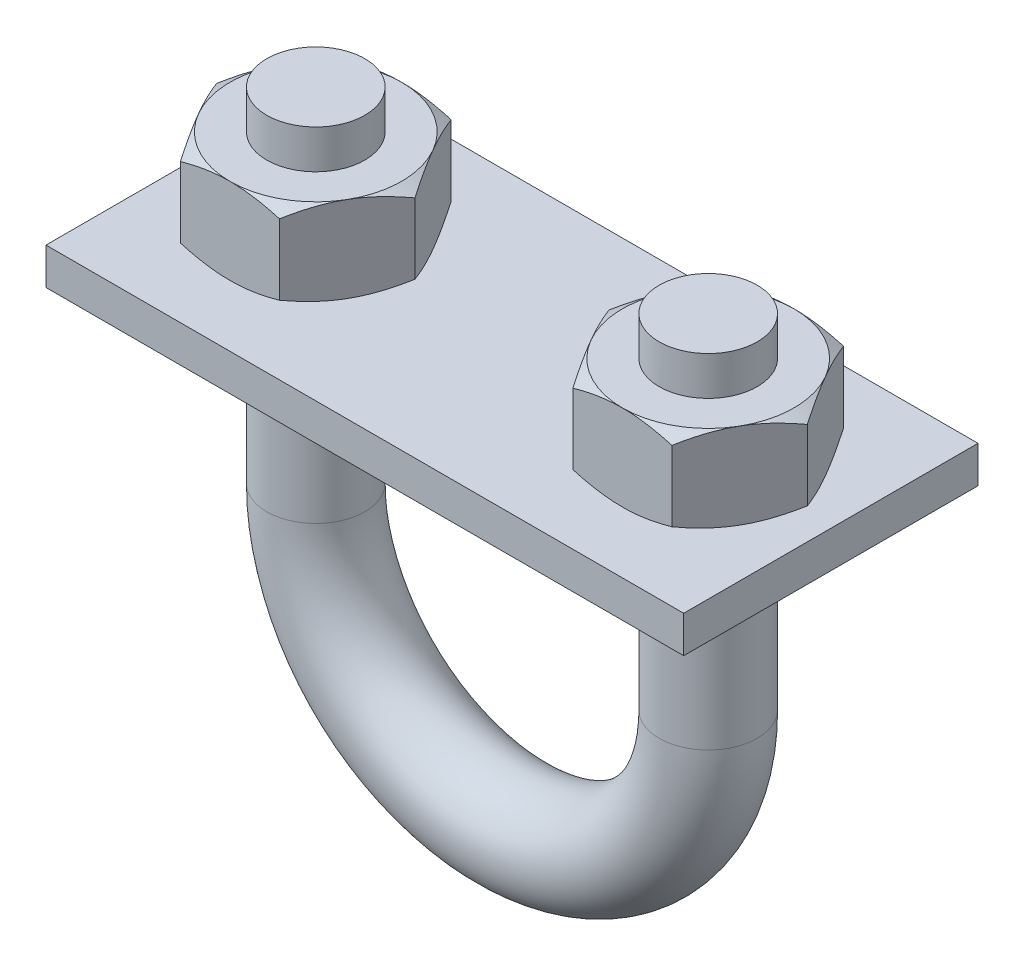
SolidWorks part; units mm, degrees
ref_plane "Front" through (0, 0, 0) normal (0, 0, 1) x (1, 0, 0)
ref_plane "Top" through (0, 0, 0) normal (0, 1, 0) x (1, 0, 0)
ref_plane "Right" through (0, 0, 0) normal (1, 0, 0) x (0, 0, -1)
sketch "Sketch1" plane through (0, 0, 0) normal (0, 0, 1) x (1, 0, 0)
  line L0 (-9.525, 22.225) -> (-15.875, 22.225) construction
  line L1 (-12.7, 22.225) -> (-12.7, 0) construction
  line L3 (12.7, 0) -> (12.7, 22.225) construction
  line L4 (15.875, 22.225) -> (9.525, 22.225) construction
  line L5 (-9.525, 6.35) -> (-15.875, 6.35)
  line L6 (0, -9.525) -> (0, -15.875) construction
  arc A0 (-12.7, 0) -> (12.7, 0) centre (0, 0) ccw construction
  circle A1 centre (0, 0) radius 9.525 construction
  point P5 (0, -12.7)
  point P8 (-12.7, 16.9333)
  point P15 (-12.7, 11.6417)
  dimension "Dia" = 6.35
  dimension "D5" = 5.2917
  dimension "D6" = 5.2917
ref_plane "Plane3" through (0, 22.225, 0) normal (0, 1, 0) x (-1, 0, 0)
sketch "Sketch2" plane through (0, 22.225, 0) normal (0, 1, 0) x (-1, 0, 0)
  circle A0 centre (12.7, 0) radius 3.175
extrude "Boss-Extrude1" add sketch "Sketch2" against normal up to vertex (15.875 mm away) up to point (-9.525, 6.35, 0)
sketch "Sketch6" plane through (0, 22.225, 0) normal (0, 1, 0) x (1, 0, 0)
  circle A1 centre (-12.7, 0) radius 3.175
  circle A2 centre (-12.7, 0) radius 3.175
  dimension "D1" = 0
curve "Helix/Spiral1" pitch 1.27 height 17.145 turns 13.5 parameters "Pitch"=1.27
chamfer "Chamfer2" [suppressed] distance 0.9525 angle 45
sketch "Sketch4" plane through (0, 0, 0) normal (0, 0, 1) x (1, 0, 0)
  line L0 (-9.525, 22.225) -> (-9.525, 23.3362)
  line L1 (-9.525, 23.3362) -> (-10.3499, 22.86)
  line L2 (-10.3499, 22.86) -> (-10.3499, 22.7012)
  line L3 (-10.3499, 22.7012) -> (-9.525, 22.225)
  line L4 (-10.3499, 22.7806) -> (-9.525, 22.7806) construction
  line L5 (-9.9374, 23.0981) -> (-9.9374, 22.4631) construction
  line L7 (-9.525, 22.225) -> (-15.875, 22.225) construction
  dimension "D1" = 60
  dimension "D2" = 0.635
  dimension "D3" = 0.1588
sweep "Threads" [suppressed] cut profiles "Sketch4" path "Helix/Spiral1"
ref_plane "Plane5" through (0, 6.35, 0) normal (0, 1, 0) x (-1, 0, 0)
sketch "Sketch7" plane through (0, 6.35, 0) normal (0, 1, 0) x (-1, 0, 0)
  line L0 (9.525, 0) -> (15.875, 0) construction
  circle A0 centre (12.7, 0) radius 3.175
  circle A1 centre (12.7, 0) radius 3.175 construction
sketch "Sketch8" plane through (0, 0, 0) normal (0, 0, 1) x (1, 0, 0)
  line L0 (-12.7, 22.225) -> (-12.7, 0) construction
  line L1 (12.7, 0) -> (12.7, 22.225) construction
  line L2 (-12.7, 6.35) -> (-12.7, 0)
  line L3 (12.7, 0) -> (12.7, 6.35)
  line L4 (47.1487, 6.35) -> (-47.1487, 6.35) construction
  arc A0 (-12.7, 0) -> (12.7, 0) centre (0, 0) ccw construction
  arc A1 (-12.7, 0) -> (12.7, 0) centre (0, 0) ccw
sweep "Sweep1" add profiles "Sketch7" path "Sketch8"
move or copy body "Body-Move/Copy1" bodies to move or copy 109 copy yes number of copies 1 translate (25.4, 0, 0)
combine bodies "Combine1" operation type add bodies to combine 109 112 111
ref_plane "Plane6" through (0, 16.9333, 0) normal (0, 1, 0) x (-1, 0, 0)
sketch "Sketch9" plane through (0, 16.9333, 0) normal (0, 1, 0) x (-1, 0, 0)
  line L0 (-15.875, 0) -> (-9.525, 0) construction
  line L1 (-15.9079, 5.5562) -> (-19.1158, 0)
  line L2 (-19.1158, 0) -> (-15.9079, -5.5563)
  line L3 (-15.9079, -5.5563) -> (-9.4921, -5.5563)
  line L4 (-9.4921, -5.5563) -> (-6.2842, 0)
  line L5 (-6.2842, 0) -> (-9.4921, 5.5562)
  line L6 (-9.4921, 5.5562) -> (-15.9079, 5.5562)
  circle A0 centre (-12.7, 0) radius 5.5562 construction
  circle A1 centre (-12.7, 0) radius 3.175
  circle A2 centre (12.7, 0) radius 3.175 construction
  dimension "Nut Size" = 11.1125
extrude "Boss-Extrude2" add sketch "Sketch9" along normal mid plane 5.5562 separate body
sketch "Sketch10" plane through (0, 19.7115, 0) normal (0, 1, 0) x (1, 0, 0)
  circle A0 centre (12.7, 0) radius 5.5562 construction
  circle A1 centre (12.7, 0) radius 5.5562
extrude "Cut-Extrude1" cut sketch "Sketch10" against normal through all draft 60 flip side to cut
sketch "Sketch11" plane through (0, 14.1552, 0) normal (0, -1, 0) x (1, 0, 0)
  circle A1 centre (12.7, 0) radius 5.5562
  circle A2 centre (12.7, 0) radius 5.5562
  dimension "D1" = 0
extrude "Cut-Extrude2" cut sketch "Sketch11" against normal through all draft 60 flip side to cut
move or copy body "Body-Move/Copy2" bodies to move or copy 116 copy yes number of copies 1 translate (-25.4, 0, 0)
move or copy body "2nd set nuts" [suppressed] bodies to move or copy 117 116 copy yes number of copies 1 translate (0, -5.2917, 0)
sketch "Sketch12" plane through (0, 14.1552, 0) normal (0, 1, 0) x (1, 0, 0)
  line L1 (20.6375, -9.525) -> (-20.6375, -9.525)
  line L2 (20.6375, -9.525) -> (20.6375, 9.525)
  line L3 (20.6375, 9.525) -> (-20.6375, 9.525)
  line L4 (-20.6375, -9.525) -> (-20.6375, 9.525)
  line L5 (20.6375, -9.525) -> (-20.6375, 9.525) construction
  line L6 (20.6375, 9.525) -> (-20.6375, -9.525) construction
  point P0 (0, 0)
  dimension "Mounting Plate Lg" = 41.275
  dimension "Mounting Plate Wd" = 19.05
extrude "Boss-Extrude3" add sketch "Sketch12" against normal blind 2.3813 separate body
ref_plane "Plane7" through (0, -9.525, 0) normal (0, 1, 0) x (1, 0, 0)
equation "\"D3@Helix/Spiral1\" = \"Thread Lg@Sketch1\"+\"Pitch@Helix/Spiral1\""
equation "\"D3@Sketch4\" = \"Pitch@Helix/Spiral1\"*.125"
equation "\"D2@Sketch4\" = \"Pitch@Helix/Spiral1\"*.5"
equation "\"D1@Chamfer2\" = \"Pitch@Helix/Spiral1\"*.75"
equation "\"D5@Sketch1\" = \"Thread Lg@Sketch1\"/3"
equation "\"D6@Sketch1\" = \"Thread Lg@Sketch1\"/3"
